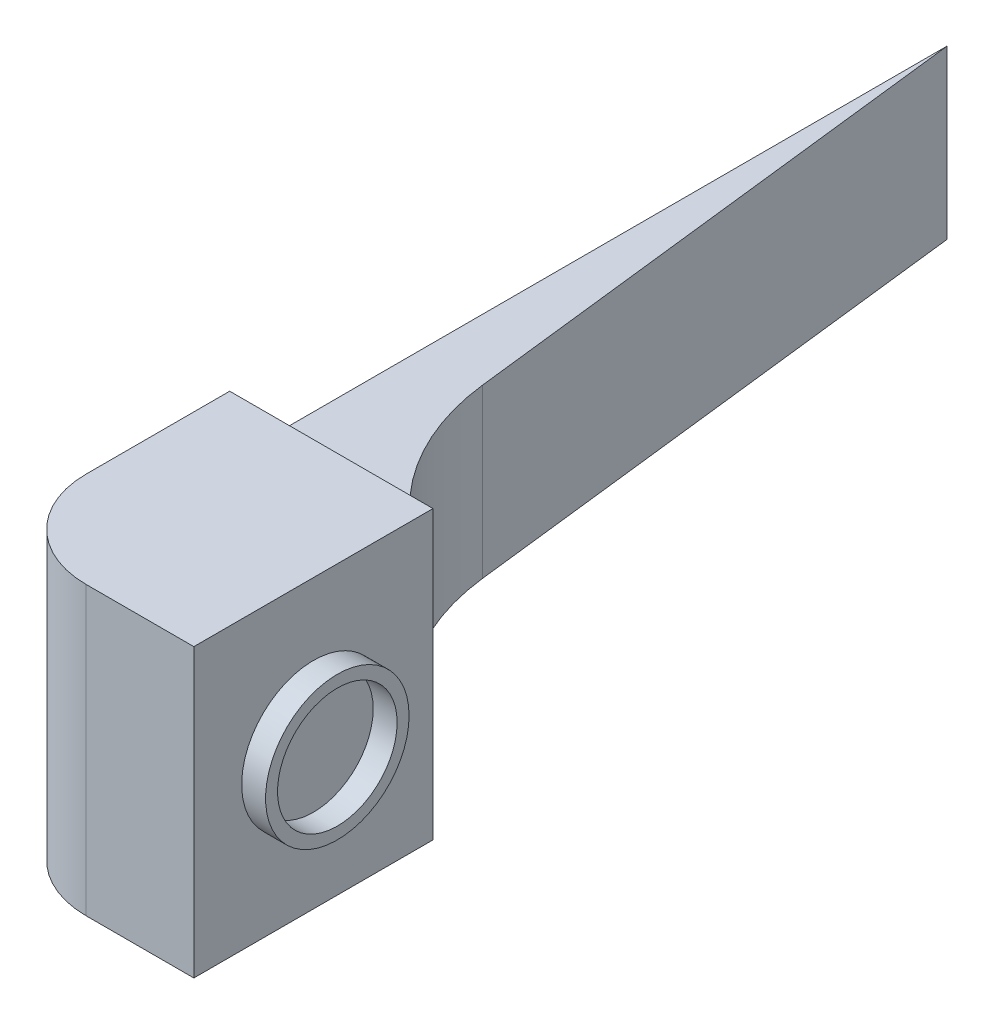
SolidWorks part; units mm, degrees
other "Markup1"
sketch "Sketch4" plane through (10, 0, 0) normal (0.9575, -0.2153, 0.1921) x (0.1497, -0.1986, -0.9686)
ref_plane "Front Plane" through (0, 0, 0) normal (0, 0, 1) x (1, 0, 0)
ref_plane "Top Plane" through (0, 0, 0) normal (0, 1, 0) x (1, 0, 0)
ref_plane "Right Plane" through (0, 0, 0) normal (1, 0, 0) x (0, 0, -1)
sketch "Sketch1" plane through (0, 0, 0) normal (0, 1, 0) x (1, 0, 0)
  line L0 (0, 54.4323) -> (0, -54.4323) construction
  line L1 (35.0636, 0) -> (-35.0636, 0) construction
  line L2 (1.5, 40) -> (1.5, 0)
  line L3 (20, 10) -> (25, 10)
  line L4 (20, 10) -> (20, 0)
  line L5 (20, 0) -> (25, 0)
  line L6 (25, 10) -> (25, 0)
  line L7 (20, 10) -> (25, 0) construction
  line L8 (20, 0) -> (25, 10) construction
  line L9 (1.5, 40) -> (5, 10)
  line L10 (5, 10) -> (10, 10)
  line L11 (10, 10) -> (10, 0)
  line L12 (10, 0) -> (1.5, 0)
  line L13 (-10, -1.545) -> (-1.5, -1.545)
  line L14 (-10, 8.455) -> (-10, -1.545)
  line L15 (-5, 8.455) -> (-10, 8.455)
  line L16 (-1.5, 38.455) -> (-5, 8.455)
  line L17 (-1.5, 38.455) -> (-1.5, -1.545)
  point P4 (22.5, 5)
  point P15 (0, 0)
  dimension "D1" = 5
  dimension "D2" = 10
  dimension "D3" = 40
  dimension "D4" = 10
  dimension "D5" = 5
  dimension "D6" = 1.5
  dimension "D7" = 25
extrude "Boss-Extrude1" add sketch "Sketch1" along normal blind 12 contours L12 L11 L10 L9 L2 region at (4.5727, 0, -10.7273)
sketch "Sketch2" plane through (1.5, 0, 0) normal (-1, 0, 0) x (0, 0, 1)
  line L0 (0, 0) -> (-40, 0) construction
  line L1 (-10, 0) -> (-10, 12) construction
  line L2 (-10, 2.5) -> (-40, 2.5)
  line L3 (-40, 12) -> (-40, 0) construction
  line L4 (-40, 2.5) -> (-40, 0)
  line L5 (-40, 0) -> (-10, 0)
  line L6 (-10, 0) -> (-10, 2.5)
  dimension "D1" = 2.5
extrude "Cut-Extrude1" cut sketch "Sketch2" against normal blind 10
fillet "Fillet1" radius 10 1 edges at (5, 7.25, -10)
fillet "Fillet2" radius 4 1 edges at (1.5, 6, 0)
sketch "Sketch3" plane through (10, 0, 0) normal (1, 0, 0) x (0, 0, -1)
  line L0 (10, 1) -> (9, 1)
  line L1 (10, 2.5) -> (10, 0) construction
  line L2 (9, 1) -> (9, 0)
  line L3 (10, 0) -> (0, 0) construction
  line L4 (0, 1) -> (1, 1)
  line L5 (0, 12) -> (0, 0) construction
  line L6 (1, 1) -> (1, 0)
  dimension "D1" = 1
  dimension "D2" = 1
  dimension "D3" = 1
sketch "Sketch5" plane through (10, 0, 0) normal (1, 0, 0) x (0, 0, -1)
  line L0 (10, 12) -> (10, 2.5) construction
  line L1 (0, 12) -> (10, 12)
  line L2 (0, 12) -> (0, 9.5)
  line L3 (0, 9.5) -> (10, 9.5)
  line L4 (10, 12) -> (10, 9.5)
  line L6 (10, 12) -> (67.9514, 12)
  line L7 (10, 12) -> (10, 9.5)
  line L8 (10, 9.5) -> (67.9514, 9.5)
  line L9 (67.9514, 12) -> (67.9514, 9.5)
  line M4 (10, 2.5) -> (10, 12)
  dimension "D1" = 2.5
extrude "Cut-Extrude2" cut sketch "Sketch5" against normal through all contours L9 L6 L8 M4 region at (10, 10.75, -38.9757)
fillet "Fillet3" radius 1 1 edges at (5.75, 9.5, -10)
fillet "Fillet4" radius 1 1 edges at (5.75, 2.5, -10)
sketch "Sketch6" plane through (10, 0, 0) normal (1, 0, 0) x (0, 0, -1)
  line L0 (5, 12) -> (5, 0) construction
  line L1 (10, 12) -> (0, 12) construction
  line L2 (10, 0) -> (0, 0) construction
  circle A0 centre (5, 6) radius 2.5
  circle A1 centre (5, 6) radius 3
  dimension "D1" = 5
  dimension "D2" = 0.5
extrude "Boss-Extrude2" add sketch "Sketch6" along normal blind 1
